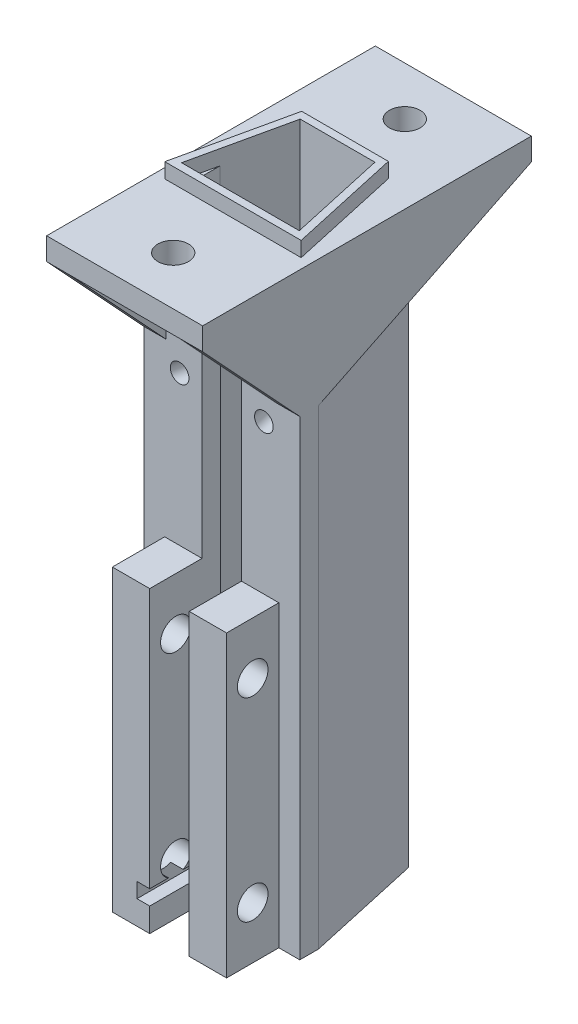
SolidWorks part; units mm, degrees
ref_plane "Front Plane" through (0, 0, 0) normal (0, 0, 1) x (1, 0, 0)
ref_plane "Top Plane" through (0, 0, 0) normal (0, 1, 0) x (1, 0, 0)
ref_plane "Right Plane" through (0, 0, 0) normal (1, 0, 0) x (0, 0, -1)
sketch "Sketch2" plane through (0, 0, 0) normal (0, 1, 0) x (1, 0, 0)
  line L0 (-8.2446, 3.8436) -> (5.7683, 3.8436)
  line L1 (-8.2446, 3.8436) -> (-8.2446, 1.3436)
  line L2 (5.7683, 3.8436) -> (5.7683, 1.3436)
  line L3 (-8.2446, 1.3436) -> (5.7683, 1.3436)
  line L4 (5.7683, 3.8436) -> (9.2046, -11.6564)
  line L5 (5.7683, 3.8436) -> (3.3276, 3.3025)
  line L6 (9.2046, -11.6564) -> (6.7639, -12.1975)
  line L7 (3.3276, 3.3025) -> (6.7639, -12.1975)
  line L8 (-8.2446, 3.8436) -> (-11.6809, -11.6564)
  line L9 (-8.2446, 3.8436) -> (-5.8038, 3.3025)
  line L10 (-11.6809, -11.6564) -> (-9.2401, -12.1975)
  line L11 (-5.8038, 3.3025) -> (-9.2401, -12.1975)
  line L12 (-11.6809, -11.6564) -> (-3.8809, -11.6564)
  line L13 (-11.6809, -11.6564) -> (-11.6809, -14.1564)
  line L14 (-3.8809, -11.6564) -> (-3.8809, -14.1564)
  line L15 (-11.6809, -14.1564) -> (-3.8809, -14.1564)
  line L16 (9.2046, -11.6564) -> (1.4046, -11.6564)
  line L17 (9.2046, -11.6564) -> (9.2046, -14.1564)
  line L18 (1.4046, -11.6564) -> (1.4046, -14.1564)
  line L19 (9.2046, -14.1564) -> (1.4046, -14.1564)
  line L20 (-3.8809, -14.1564) -> (-8.8809, -14.1564)
  line L21 (-3.8809, -14.1564) -> (-3.8809, -21.1564)
  line L22 (-8.8809, -14.1564) -> (-8.8809, -21.1564)
  line L23 (-3.8809, -21.1564) -> (-8.8809, -21.1564)
  line L24 (1.4046, -14.1564) -> (6.4046, -14.1564)
  line L25 (1.4046, -14.1564) -> (1.4046, -21.1564)
  line L26 (6.4046, -14.1564) -> (6.4046, -21.1564)
  line L27 (1.4046, -21.1564) -> (6.4046, -21.1564)
  point P0 (-6.2381, 1.3436)
  point P21 (3.7619, 1.3436)
  point P24 (6.6439, -11.6564)
  point P25 (-9.1202, -11.6564)
  dimension "D1" = 0
  dimension "D2" = 2.5
  dimension "D3" = 2.5
  dimension "D4" = 2.5
  dimension "D5" = 10
  dimension "D6" = 360
  dimension "D7" = 13
  dimension "D8" = 2.5
  dimension "D9" = 2.5
  dimension "D10" = 13
  dimension "D11" = 5
  dimension "D12" = 5
  dimension "D13" = 102.5
  dimension "D14" = 7.8
  dimension "D15" = 7.8
  dimension "D16" = 102.5
  dimension "D17" = 15.7641
  dimension "D18" = 5.2855
  dimension "D19" = 7
  dimension "D20" = 7
extrude "Boss-Extrude1" add sketch "Sketch2" along normal blind 40 contours L16 L4 L2 L3 L7 | L9 L11 L3 L7 L5 L0 | L8 L12 L11 L3 L1 | L5 L7 L3 L2 | L11 L9 L1 L3 | L13 L15 L14 L12 L11 L10 | L12 L10 L11 | L6 L16 L7 | L19 L17 L6 L7 L16 L18 | L25 L27 L26 L19 | L23 L21 L15 L22 region at (-7.169, 0, -2.5034) region at (-8.9487, 0, 5.0069) region at (-1.2381, 0, -2.6298) region at (6.4724, 0, 5.0069) region at (4.6927, 0, -2.5034) region at (-10.0137, 0, 11.8368) region at (-7.6986, 0, 12.9458) region at (5.2224, 0, 12.9458) region at (7.5375, 0, 11.8368) region at (-6.3809, 0, 17.6564) region at (3.9046, 0, 17.6564)
sketch "Sketch3" plane through (-8.8809, 0, 0) normal (-1, 0, 0) x (0, 0, 1)
  line L0 (21.1564, 40) -> (21.1564, 0) construction
  line L1 (14.1564, 40) -> (14.1564, 0) construction
  line L2 (14.1564, 40) -> (21.1564, 40) construction
  line L3 (14.1564, 0) -> (21.1564, 0) construction
  circle A0 centre (17.6564, 33) radius 2.05
  circle A1 centre (17.6564, 7) radius 2.05
  dimension "D5" = 4.1
  dimension "D6" = 4.1
  dimension "D1" = 3.5
  dimension "D2" = 3.5
  dimension "D3" = 3.5
  dimension "D4" = 3.5
  dimension "D7" = 7
  dimension "D8" = 7
extrude "Cut-Extrude2" cut sketch "Sketch3" against normal blind 40
sketch "Sketch4" plane through (0, 40, 0) normal (0, 1, 0) x (1, 0, 0)
  line L0 (-9.1202, -11.6564) -> (-6.2381, 1.3436)
  line L1 (-6.2381, 1.3436) -> (3.7619, 1.3436)
  line L2 (3.7619, 1.3436) -> (6.6439, -11.6564)
  line L3 (6.6439, -11.6564) -> (1.4046, -11.6564)
  line L4 (1.4046, -11.6564) -> (1.4046, -14.1564)
  line L5 (1.4046, -11.6564) -> (1.4046, -21.1564) construction
  line L6 (1.4046, -14.1564) -> (9.2046, -14.1564)
  line L7 (9.2046, -14.1564) -> (9.2046, -11.6564)
  line L8 (9.2046, -11.6564) -> (5.7683, 3.8436)
  line L9 (5.7683, 3.8436) -> (-8.2446, 3.8436)
  line L10 (-8.2446, 3.8436) -> (-11.6809, -11.6564)
  line L11 (-11.6809, -11.6564) -> (-11.6809, -14.1564)
  line L12 (-11.6809, -14.1564) -> (-3.8809, -14.1564)
  line L13 (-3.8809, -11.6564) -> (-3.8809, -21.1564) construction
  line L14 (-3.8809, -14.1564) -> (-3.8809, -11.6564)
  line L33 (-6.2381, 1.3436) -> (3.7619, 1.3436)
  line L34 (3.7619, 1.3436) -> (6.6439, -11.6564)
  line L35 (6.6439, -11.6564) -> (1.4046, -11.6564)
  line L36 (1.4046, -11.6564) -> (1.4046, -21.1564)
  line L37 (1.4046, -21.1564) -> (6.4046, -21.1564)
  line L38 (6.4046, -21.1564) -> (6.4046, -14.1564)
  line L39 (6.4046, -14.1564) -> (9.2046, -14.1564)
  line L40 (9.2046, -14.1564) -> (9.2046, -11.6564)
  line L41 (9.2046, -11.6564) -> (5.7683, 3.8436)
  line L42 (5.7683, 3.8436) -> (-8.2446, 3.8436)
  line L43 (-8.2446, 3.8436) -> (-11.6809, -11.6564)
  line L44 (-11.6809, -11.6564) -> (-11.6809, -14.1564)
  line L45 (-11.6809, -14.1564) -> (-8.8809, -14.1564)
  line L46 (-8.8809, -14.1564) -> (-8.8809, -21.1564)
  line L47 (-8.8809, -21.1564) -> (-3.8809, -21.1564)
  line L48 (-3.8809, -21.1564) -> (-3.8809, -11.6564)
  line L49 (-3.8809, -11.6564) -> (-9.1202, -11.6564)
  line L50 (-9.1202, -11.6564) -> (-6.2381, 1.3436)
  line L51 (-6.2381, 1.3436) -> (3.7619, 1.3436)
  line L52 (3.7619, 1.3436) -> (6.6439, -11.6564)
  line L53 (6.6439, -11.6564) -> (1.4046, -11.6564)
  line L54 (1.4046, -11.6564) -> (1.4046, -21.1564)
  line L55 (1.4046, -21.1564) -> (6.4046, -21.1564)
  line L56 (6.4046, -21.1564) -> (6.4046, -14.1564)
  line L57 (6.4046, -14.1564) -> (9.2046, -14.1564)
  line L58 (9.2046, -14.1564) -> (9.2046, -11.6564)
  line L59 (9.2046, -11.6564) -> (5.7683, 3.8436)
  line L60 (5.7683, 3.8436) -> (-8.2446, 3.8436)
  line L61 (-8.2446, 3.8436) -> (-11.6809, -11.6564)
  line L62 (-11.6809, -11.6564) -> (-11.6809, -14.1564)
  line L63 (-11.6809, -14.1564) -> (-8.8809, -14.1564)
  line L64 (-8.8809, -14.1564) -> (-8.8809, -21.1564)
  line L65 (-8.8809, -21.1564) -> (-3.8809, -21.1564)
  line L66 (-3.8809, -21.1564) -> (-3.8809, -11.6564)
  line L68 (-9.1202, -11.6564) -> (-6.2381, 1.3436)
  line M19 (-6.2381, 1.3436) -> (3.7619, 1.3436)
  line M20 (3.7619, 1.3436) -> (6.6439, -11.6564)
  line M21 (6.6439, -11.6564) -> (1.4046, -11.6564)
  line M22 (1.4046, -11.6564) -> (1.4046, -21.1564)
  line M25 (6.4046, -14.1564) -> (9.2046, -14.1564)
  line M26 (9.2046, -14.1564) -> (9.2046, -11.6564)
  line M27 (9.2046, -11.6564) -> (5.7683, 3.8436)
  line M28 (5.7683, 3.8436) -> (-8.2446, 3.8436)
  line M29 (-8.2446, 3.8436) -> (-11.6809, -11.6564)
  line M30 (-11.6809, -11.6564) -> (-11.6809, -14.1564)
  line M31 (-11.6809, -14.1564) -> (-8.8809, -14.1564)
  line M34 (-3.8809, -21.1564) -> (-3.8809, -11.6564)
  line M35 (-3.8809, -11.6564) -> (-9.1202, -11.6564)
  line M36 (-9.1202, -11.6564) -> (-6.2381, 1.3436)
  dimension "D1" = 0
extrude "Boss-Extrude2" add sketch "Sketch4" along normal blind 40 contours L12 L6 M31 M34 M35 M36 M19 M20 M21 M22 M25 M26 M27 M28 M29 M30 region at (-6.5005, 40, 11.9321)
sketch "Sketch7" plane through (0, 0, -3.8436) normal (0, 0, -1) x (-1, 0, 0)
  line L0 (-5.7683, 80) -> (-5.7683, 0) construction
  line L1 (5.4917, 3.2) -> (0.9917, 3.2)
  line L2 (5.4917, 3.2) -> (5.4917, 5.2)
  line L3 (5.4917, 5.2) -> (0.9917, 5.2)
  line L4 (0.9917, 3.2) -> (0.9917, 5.2)
  line L5 (8.2446, 80) -> (8.2446, 0) construction
  line L6 (8.2446, 0) -> (-5.7683, 0) construction
  point P4 (0.9917, 4.2)
  dimension "D1" = 6.76
  dimension "D2" = 4.5
  dimension "D3" = 2
  dimension "D4" = 2.7529
  dimension "D5" = 3.2
extrude "Cut-Extrude3" cut sketch "Sketch7" against normal through all
sketch "Sketch8" plane through (0, 0, 11.6564) normal (0, 0, -1) x (-1, 0, 0)
  line L0 (3.8809, 80) -> (3.8809, 5.2) construction
  line L1 (5.5809, 5.2) -> (3.8809, 5.2)
  line L2 (5.5809, 5.2) -> (5.5809, 3.2)
  line L3 (5.5809, 3.2) -> (3.8809, 3.2)
  line L4 (3.8809, 5.2) -> (3.8809, 3.2)
  line L5 (9.1202, 0) -> (3.8809, 0) construction
  dimension "D1" = 2
  dimension "D2" = 1.7
  dimension "D3" = 3.2
extrude "Cut-Extrude4" cut sketch "Sketch8" against normal through all
sketch "Sketch9" plane through (0, 80, 0) normal (0, 1, 0) x (1, 0, 0)
  line L0 (1.4046, -11.6564) -> (1.4046, -12.6564)
  line L1 (1.4046, -11.6564) -> (1.4046, -14.1564) construction
  line L2 (1.4046, -11.6564) -> (6.6439, -11.6564)
  line L3 (6.6439, -11.6564) -> (3.7619, 1.3436)
  line L4 (3.7619, 1.3436) -> (-6.2381, 1.3436)
  line L5 (-6.2381, 1.3436) -> (-9.1202, -11.6564)
  line L6 (-9.1202, -11.6564) -> (-3.8809, -11.6564)
  line L7 (-3.8809, -11.6564) -> (-3.8809, -12.6564)
  line L8 (-3.8809, -14.1564) -> (-3.8809, -11.6564) construction
  line L9 (-3.8809, -12.6564) -> (-10.3661, -12.6564)
  line L10 (-10.3661, -12.6564) -> (-7.0407, 2.3436)
  line L11 (-7.0407, 2.3436) -> (4.5645, 2.3436)
  line L12 (4.5645, 2.3436) -> (7.8899, -12.6564)
  line L13 (7.8899, -12.6564) -> (1.4046, -12.6564)
  line L14 (1.4046, -12.6564) -> (-3.8809, -12.6564)
  line L15 (-3.8809, -11.6564) -> (1.4046, -11.6564)
  line M8 (-3.8809, -14.1564) -> (-3.8809, -11.6564)
  line M9 (-3.8809, -11.6564) -> (-9.1202, -11.6564)
  line M10 (-9.1202, -11.6564) -> (-6.2381, 1.3436)
  line M11 (-6.2381, 1.3436) -> (3.7619, 1.3436)
  line M12 (3.7619, 1.3436) -> (6.6439, -11.6564)
  line M13 (6.6439, -11.6564) -> (1.4046, -11.6564)
  line M14 (1.4046, -11.6564) -> (1.4046, -14.1564)
  dimension "D2" = 1
  dimension "D3" = 1
  dimension "D4" = 1
  dimension "D5" = 1
  dimension "D6" = 11.6052
extrude "Boss-Extrude3" add sketch "Sketch9" along normal blind 2 contours L13 L12 L11 L10 L9 M8 M9 M10 M11 M12 M13 M14 | L15 L14 M8 M14 region at (4.0243, 80, 11.8927) region at (-1.2381, 80, 12.1564)
sketch "Sketch10" plane through (0, 0, -3.8436) normal (0, 0, -1) x (-1, 0, 0)
  line L0 (5.4917, 5.2) -> (0.9917, 5.2)
  line L1 (5.4917, 5.2) -> (5.4917, 80.2)
  line L2 (0.9917, 5.2) -> (0.9917, 80.2)
  line L3 (5.4917, 80.2) -> (0.9917, 80.2)
  dimension "D1" = 75
extrude "Cut-Extrude5" cut sketch "Sketch10" against normal blind 1.5
sketch "Sketch13" plane through (0, 0, -2.3436) normal (0, 0, -1) x (-1, 0, 0)
  line L1 (5.4917, 5.2) -> (8.2917, 5.2)
  line L2 (5.4917, 5.2) -> (5.4917, 7.2)
  line L3 (5.4917, 7.2) -> (8.2917, 7.2)
  line L4 (8.2917, 5.2) -> (8.2917, 7.2)
  dimension "D1" = 2
  dimension "D2" = 2.8
extrude "Cut-Extrude7" cut sketch "Sketch13" along normal blind 1.5
sketch "Sketch15" plane through (0, 0, -3.8436) normal (0, 0, -1) x (-1, 0, 0)
  line L0 (8.2446, 7.2) -> (5.4917, 7.2) construction
  line L1 (8.2446, 5.2) -> (6.7446, 5.2)
  line L2 (8.2446, 5.2) -> (8.2446, 7.2)
  line L3 (8.2446, 7.2) -> (6.7446, 7.2)
  line L4 (6.7446, 5.2) -> (6.7446, 7.2)
  dimension "D1" = 1.5
extrude "Cut-Extrude8" cut sketch "Sketch15" along direction (-0.2164, 0, 0.9763) on the side against the normal blind 18.5
sketch "Sketch16" plane through (0, 0, 14.1564) normal (0, 0, 1) x (1, 0, 0)
  line L0 (-3.8809, 80) -> (-3.8809, 40) construction
  line L2 (-10.3661, 80) -> (-3.8809, 80) construction
  circle A0 centre (-6.8809, 60) radius 1.25
  point P8 (0, 0)
  dimension "D1" = 20
  dimension "D2" = 2.5
  dimension "D4" = 3
extrude "Cut-Extrude9" cut sketch "Sketch16" along direction (-0.2164, 0, 0.9763) on the side against the normal blind 3.5
sketch "Sketch17" plane through (0, 0, 14.1564) normal (0, 0, 1) x (1, 0, 0)
  line L0 (1.4046, 80) -> (1.4046, 40) construction
  line L1 (1.4046, 80) -> (9.2046, 80) construction
  circle A0 centre (4.4046, 60) radius 1.25
  dimension "D1" = 2.5
  dimension "D2" = 3
  dimension "D3" = 20
extrude "Cut-Extrude10" cut sketch "Sketch17" along direction (0.2164, 0, 0.9763) on the side against the normal blind 3.5
sketch "Sketch18" plane through (0, 0, 11.6564) normal (0, 0, -1) x (-1, 0, 0)
  line L0 (-9.2046, 80) -> (-9.2046, 0) construction
  line L1 (-9.2046, 80) -> (11.6809, 80)
  line L2 (-9.2046, 80) -> (-9.2046, 77)
  line L3 (-9.2046, 77) -> (11.6809, 77)
  line L4 (11.6809, 80) -> (11.6809, 77)
  line L5 (11.6809, 80) -> (11.6809, 7.2) construction
  dimension "D1" = 3
  dimension "D2" = 0
extrude "Boss-Extrude4" add sketch "Sketch18" against normal blind 15.5
sketch "Sketch19" plane through (0, 0, -3.8436) normal (0, 0, -1) x (-1, 0, 0)
  line L0 (-5.7683, 80) -> (-5.7683, 0) construction
  line L1 (8.2446, 80) -> (-5.7683, 80)
  line L2 (8.2446, 80) -> (8.2446, 77)
  line L3 (8.2446, 77) -> (-5.7683, 77)
  line L4 (-5.7683, 80) -> (-5.7683, 77)
  dimension "D1" = 3
extrude "Boss-Extrude5" add sketch "Sketch19" along normal blind 13 and the other way blind 2 contours L1 L4 L3 L2
sketch "Sketch21" plane through (-11.6809, 0, 0) normal (-1, 0, 0) x (0, 0, 1)
  line L0 (27.1564, 77) -> (14.1564, 63)
  line L1 (14.1564, 77) -> (14.1564, 7.2) construction
  line L2 (14.1564, 63) -> (14.1564, 77)
  line L3 (14.1564, 77) -> (27.1564, 77)
  dimension "D1" = 14
extrude "Boss-Extrude6" add sketch "Sketch21" against normal blind 3
sketch "Sketch22" plane through (9.2046, 0, 0) normal (1, 0, 0) x (0, 0, -1)
  line L0 (-27.1564, 77) -> (-14.1564, 77)
  line L1 (-14.1564, 77) -> (-14.1564, 63)
  line L2 (-14.1564, 77) -> (-14.1564, 0) construction
  line L3 (-14.1564, 63) -> (-27.1564, 77)
  dimension "D1" = 14
extrude "Boss-Extrude8" add sketch "Sketch22" against normal blind 3
sketch "Sketch23" plane through (9.2046, 0, 0) normal (1, 0, 0) x (0, 0, -1)
  line L0 (-11.6564, 80) -> (-11.6564, 63)
  line L1 (-11.6564, 80) -> (-11.6564, 0) construction
  line L2 (16.8436, 80) -> (16.8436, 77)
  line L3 (16.8436, 80) -> (-11.6564, 80)
  line L4 (16.8436, 77) -> (-11.6564, 63)
  dimension "D1" = 28.5
  dimension "D2" = 28.5
  dimension "D3" = 17
  dimension "D4" = 3
extrude "Boss-Extrude9" add sketch "Sketch23" against normal blind 3.5
sketch "Sketch24" plane through (-11.6809, 0, 0) normal (-1, 0, 0) x (0, 0, 1)
  line L0 (11.6564, 80) -> (-16.8436, 80)
  line L1 (-16.8436, 80) -> (-16.8436, 77)
  line L2 (-16.8436, 77) -> (11.6564, 63)
  line L3 (11.6564, 80) -> (11.6564, 7.2) construction
  line L4 (11.6564, 63) -> (11.6564, 80)
  dimension "D1" = 17
  dimension "D2" = 28.5
  dimension "D3" = 3
extrude "Boss-Extrude10" add sketch "Sketch24" against normal blind 3.5
sketch "Sketch25" plane through (0, 80, 0) normal (0, 1, 0) x (1, 0, 0)
  line L0 (-7.0407, 2.3436) -> (4.5645, 2.3436) construction
  line L1 (7.8899, -12.6564) -> (-10.3661, -12.6564) construction
  circle A0 centre (-1.2381, 10.3436) radius 2.05
  circle A1 centre (-1.2381, -20.6564) radius 2.05
  point P11 (0, 0)
  point P12 (-1.6325, -20.199)
  dimension "D1" = 4.1
  dimension "D2" = 4.1
  dimension "D3" = 8
  dimension "D4" = 8
  dimension "D5" = 9.128
  dimension "D6" = 9.128
  dimension "D7" = 5.8026
  dimension "D8" = 5.8026
extrude "Cut-Extrude12" cut sketch "Sketch25" against normal blind 3.5
